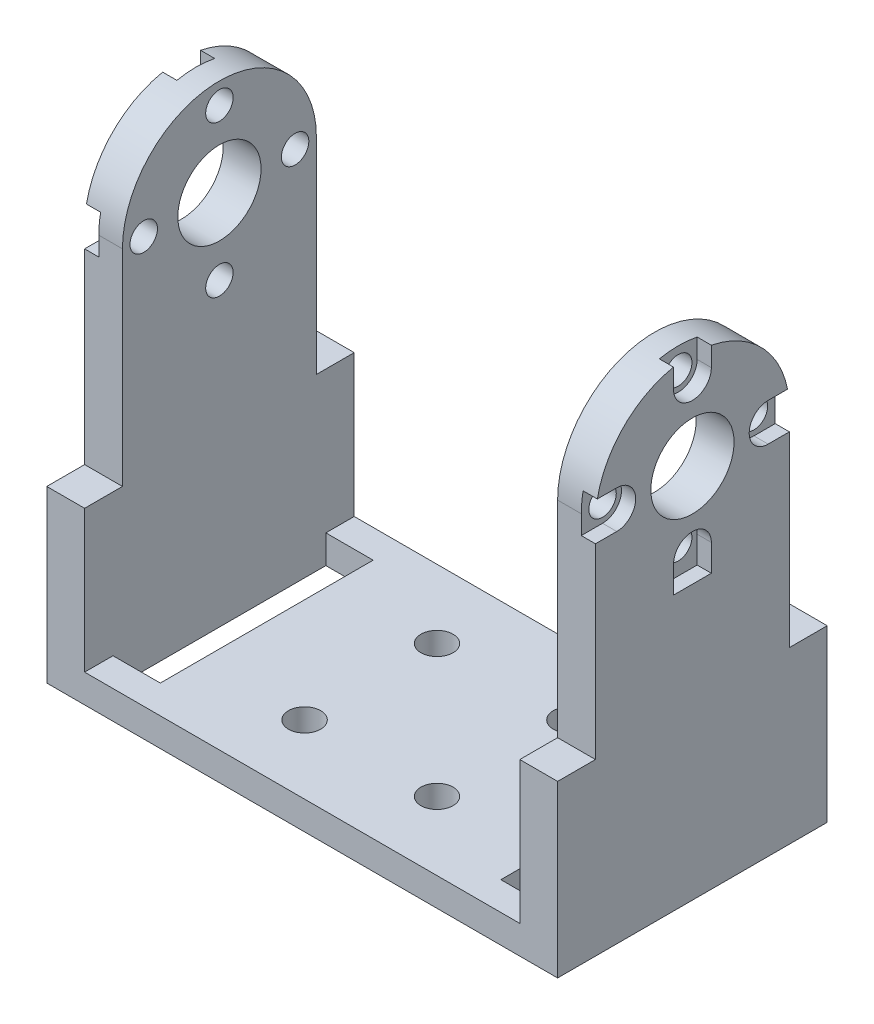
SolidWorks part; units mm, degrees
ref_plane "Front Plane" through (0, 0, 0) normal (0, 0, 1) x (1, 0, 0)
ref_plane "Top Plane" through (0, 0, 0) normal (0, 1, 0) x (1, 0, 0)
ref_plane "Right Plane" through (0, 0, 0) normal (1, 0, 0) x (0, 0, -1)
sketch "Sketch1" plane through (0, 0, 0) normal (0, 1, 0) x (1, 0, 0)
  line L0 (0, 0) -> (0, -7.6155) construction
  line L1 (-18, 14.25) -> (18, 14.25)
  line L2 (-18, 14.25) -> (-18, -14.25)
  line L3 (-18, -14.25) -> (18, -14.25)
  line L4 (18, 14.25) -> (18, -14.25)
  line L5 (0, 0) -> (0, 12.9892) construction
  line L6 (-18, 14.25) -> (-27, 14.25)
  line L7 (-18, 14.25) -> (-18, -14.25)
  line L8 (-18, -14.25) -> (-27, -14.25)
  line L9 (-27, 14.25) -> (-27, -14.25)
  line L10 (18, 14.25) -> (27, 14.25)
  line L11 (18, 14.25) -> (18, -14.25)
  line L12 (18, -14.25) -> (27, -14.25)
  line L13 (27, 14.25) -> (27, -14.25)
  line L14 (-23, 11.25) -> (-18, 11.25)
  line L15 (-23, 11.25) -> (-23, -11.25)
  line L16 (-23, -11.25) -> (-18, -11.25)
  line L17 (-18, 11.25) -> (-18, -11.25)
  line L18 (18, 11.25) -> (18, -11.25)
  line L19 (23, -11.25) -> (18, -11.25)
  line L20 (23, 11.25) -> (23, -11.25)
  line L21 (23, 11.25) -> (18, 11.25)
  circle A0 centre (0, 0) radius 7.5
  circle A1 centre (-9, 8.25) radius 1.7
  circle A2 centre (-9, -8.25) radius 1.7
  circle A3 centre (9, -8.25) radius 1.7
  circle A4 centre (9, 8.25) radius 1.7
  point P0 (0, 0)
  dimension "D3" = 9
  dimension "D4" = 8.25
  dimension "D5" = 8.25
  dimension "D6" = 9
  dimension "D7" = 9
  dimension "D9" = 15
  dimension "D14" = 3.4
  dimension "D1" = 36
  dimension "D2" = 28.5
  dimension "D8" = 9
  dimension "D10" = 4
  dimension "D11" = 3
  dimension "D12" = 3
  dimension "D13" = 5
extrude "Boss-Extrude2" add sketch "Sketch1" along normal blind 3 contours L6 L9 L8 L2 | L13 L10 L4 L12 | L4 L1 L2 L3 A3 A2 A1 A0 A4 region at (0, 0, -13.7908) region at (-24.0625, 0, 0) region at (24.0625, 0, 0)
sketch "Sketch2" plane through (0, 3, 0) normal (0, 1, 0) x (1, 0, 0)
  line L5 (27, 14.25) -> (27, -14.25) construction
  line L6 (27, 10.25) -> (23, 10.25)
  line L7 (27, 10.25) -> (27, -10.25)
  line L8 (27, -10.25) -> (23, -10.25)
  line L9 (23, 10.25) -> (23, -10.25)
  line L10 (27, 14.25) -> (-27, 14.25) construction
  dimension "D1" = 4
  dimension "D2" = 20.5
  dimension "D3" = 4
extrude "Boss-Extrude3" add sketch "Sketch2" along normal blind 21.75
sketch "Sketch4" plane through (27, 0, 0) normal (1, 0, 0) x (0, 0, -1)
  line L0 (-10.25, 24.75) -> (10.25, 24.75) construction
  circle A0 centre (0, 24.75) radius 10.25
  point P18 (0, 17.75)
  line M5 (10.25, 24.75) -> (-10.25, 24.75)
extrude "Boss-Extrude4" add sketch "Sketch4" against normal blind 4 contours A0 M5 | M5 | M5 | A0 M5 region at (27, 29.1002, 0) region at (27, 20.3998, 0)
ref_plane "Plane1" through (0, 0, 0) normal (1, 0, 0) x (0, 0, -1)
mirror "Mirror1" about plane through (0, 0, 0) normal (1, 0, 0) of "Boss-Extrude3", "Boss-Extrude4"
sketch "Sketch6" plane through (27, 0, 0) normal (1, 0, 0) x (0, 0, -1)
  line L0 (-10.25, 24.75) -> (10.25, 24.75) construction
  line L1 (0, 35) -> (0, 14.5) construction
  circle A6 centre (0, 24.75) radius 4.4
  circle A7 centre (0, 24.75) radius 8
  circle A8 centre (0, 32.75) radius 1.45
  circle A9 centre (8, 24.75) radius 1.45
  circle A10 centre (0, 16.75) radius 1.45
  circle A11 centre (-8, 24.75) radius 1.45
  circle A12 centre (0, 24.75) radius 10.25
  point P21 (0, 24.75)
  dimension "D1" = 8.8
  dimension "D2" = 16
  dimension "D3" = 4
  dimension "D4" = 2.9
extrude "Cut-Extrude3" cut sketch "Sketch6" against normal blind 4 contours A6 | A7 A11 | A7 A11 | A7 A10 | A7 A10 | A7 A9 | A7 A9 | A7 A8 | A7 A8 region at (27, 24.75, 0) region at (27, 24.75, -7.3615) region at (27, 24.75, -8.5911) region at (27, 32.1115, 0) region at (27, 33.3411, 0) region at (27, 16.1589, 0) region at (27, 17.3885, 0) region at (27, 24.75, 7.3615) region at (27, 24.75, 8.5911)
mirror "Mirror3" about plane through (0, 0, 0) normal (1, 0, 0) of "Cut-Extrude3"
sketch "Sketch7" plane through (27, 0, 0) normal (1, 0, 0) x (0, 0, -1)
  line L0 (10.8224, 26.75) -> (10.8224, 22.75)
  line L2 (-2, 32.75) -> (-2, 35.5724)
  line L3 (-2, 35.5724) -> (2, 35.5724)
  line L4 (2, 32.75) -> (2, 35.5724)
  line L5 (8, 22.75) -> (10.8224, 22.75)
  line L6 (8, 26.75) -> (10.8224, 26.75)
  line L7 (2, 13.9276) -> (-2, 13.9276)
  line L8 (-2, 16.75) -> (-2, 13.9276)
  line L9 (2, 16.75) -> (2, 13.9276)
  line L10 (-10.8224, 22.75) -> (-10.8224, 26.75)
  line L11 (-8, 26.75) -> (-10.8224, 26.75)
  line L12 (-8, 22.75) -> (-10.8224, 22.75)
  circle A0 centre (0, 32.75) radius 2
  circle A1 centre (0, 24.75) radius 8
  circle A2 centre (8, 24.75) radius 2
  circle A3 centre (0, 16.75) radius 2
  circle A4 centre (-8, 24.75) radius 2
  point P15 (0, 24.75)
  point P32 (0, 24.75)
  circle M1 centre (-8, 24.75) radius 1.45
  circle M2 centre (0, 16.75) radius 1.45
  circle M3 centre (8, 24.75) radius 1.45
  circle M4 centre (0, 32.75) radius 1.45
  line M6 (10.25, 3) -> (10.25, 24.75)
  arc M7 (10.25, 24.75) -> (-10.25, 24.75) centre (0, 24.75) ccw
  line M8 (-10.25, 24.75) -> (-10.25, 3)
  dimension "D1" = 4
  dimension "D3" = 4
  dimension "D2" = 4
  dimension "D4" = 4
extrude "Cut-Extrude4" cut sketch "Sketch7" against normal blind 1.5 contours A1 M1 | A1 M1 | A1 A0 M4 | A0 A1 M4 | A1 A2 M3 | A1 A2 M3 | A1 A3 M2 | A1 A3 M2 | L4 L3 L2 M7 | A0 L4 L2 M7 | A2 L5 L6 M6 M7 | A3 L8 L7 L9 | A4 L11 L12 M7 M8 | A4 region at (27, 25.7503, -10.155) region at (27, 26.1318, -9.3818) region at (27, 35.2508, 0) region at (27, 33.7765, -1.9541) region at (27, 26.4558, -7.7711) region at (27, 32.6276, -1.9503) region at (27, 30.7939, 0) region at (27, 26.7041, 9.0265) region at (27, 16.8724, -1.9503) region at (27, 16.9789, -1.7058) region at (27, 14.633, 0) region at (27, 24.75, 7.3615) region at (27, 24.75, 8.5911)
mirror "Mirror4" about plane through (0, 0, 0) normal (1, 0, 0) of "Cut-Extrude4"
sketch "Sketch8" plane through (0, 3, 0) normal (0, 1, 0) x (1, 0, 0)
  line L0 (27, -14.25) -> (-27, -14.25) construction
  line L1 (-14.3907, 14.25) -> (14.3907, 14.25)
  line L2 (-14.3907, 14.25) -> (-14.3907, -14.25)
  line L3 (-14.3907, -14.25) -> (14.3907, -14.25)
  line L4 (14.3907, 14.25) -> (14.3907, -14.25)
  line L5 (-14.3907, 14.25) -> (14.3907, -14.25) construction
  line L6 (-14.3907, -14.25) -> (14.3907, 14.25) construction
  point P0 (0, 0)
extrude "Boss-Extrude5" add sketch "Sketch8" against normal blind 3
sketch "Sketch9" plane through (0, 3, 0) normal (0, 1, 0) x (1, 0, 0)
  line L3 (-7, 7) -> (7, 7)
  line L4 (-7, 7) -> (-7, -7)
  line L5 (-7, -7) -> (7, -7)
  line L6 (7, 7) -> (7, -7)
  line L7 (-7, 7) -> (7, -7) construction
  line L8 (-7, -7) -> (7, 7) construction
  circle A0 centre (0, 0) radius 5
  circle A2 centre (-7, 7) radius 1.7
  circle A3 centre (7, 7) radius 1.7
  circle A4 centre (7, -7) radius 1.7
  circle A5 centre (-7, -7) radius 1.7
  dimension "D1" = 14
  dimension "D2" = 14
  dimension "D3" = 10
  dimension "D4" = 3.4
  dimension "D5" = 2
  dimension "D6" = 2
extrude "Cut-Extrude5" cut sketch "Sketch9" against normal blind 3 contours L4 A5 L5 | L5 A4 L6 | L6 A3 L3 | L3 A3 L6 | L5 A5 L4 | L6 A4 L5 | A2 region at (7.2405, 3, -7.2405) region at (6.2785, 3, -6.2785) region at (-6.2785, 3, 6.2785) region at (-7.2405, 3, 7.2405) region at (7.2405, 3, 7.2405) region at (6.2785, 3, 6.2785)
sketch "Sketch10" plane through (0, 0, 0) normal (0, -1, 0) x (1, 0, 0)
  line L1 (-27, 14.25) -> (27, 14.25)
  line L2 (-27, 14.25) -> (-27, -14.25)
  line L3 (-27, -14.25) -> (27, -14.25)
  line L4 (27, 14.25) -> (27, -14.25)
  line L5 (-23, 11.25) -> (-18, 11.25)
  line L6 (-23, 11.25) -> (-23, -11.25)
  line L7 (-23, -11.25) -> (-18, -11.25)
  line L8 (-18, 11.25) -> (-18, -11.25)
  line L9 (18, 11.25) -> (23, 11.25)
  line L10 (18, 11.25) -> (18, -11.25)
  line L11 (18, -11.25) -> (23, -11.25)
  line L12 (23, 11.25) -> (23, -11.25)
  circle A0 centre (-7, 7) radius 1.7
  circle A1 centre (-7, -7) radius 1.7
  circle A2 centre (7, -7) radius 1.7
  circle A3 centre (7, 7) radius 1.7
extrude "Boss-Extrude6" add sketch "Sketch10" along normal blind 15
sketch "Sketch11" plane through (0, 0, 14.25) normal (0, 0, 1) x (1, 0, 0)
  line L0 (23, 3) -> (23, -15) construction
  line L1 (-23, 3) -> (23, 3)
  line L2 (-23, 3) -> (-23, -12)
  line L3 (-23, -12) -> (23, -12)
  line L4 (23, 3) -> (23, -12)
  line L5 (27, -15) -> (-27, -15) construction
  dimension "D1" = 3
extrude "Cut-Extrude6" cut sketch "Sketch11" against normal through all
